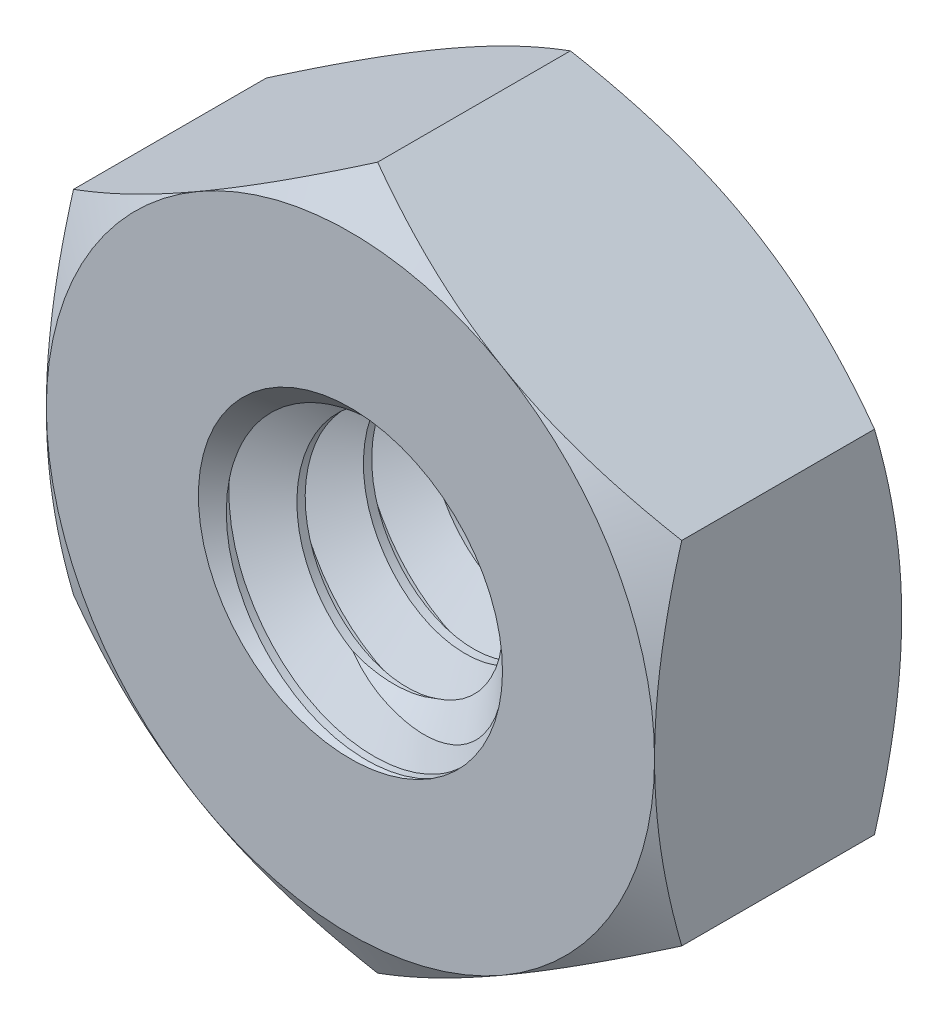
SolidWorks part; units mm, degrees
ref_plane "Front" through (0, 0, 0) normal (0, 0, 1) x (1, 0, 0)
ref_plane "Top" through (0, 0, 0) normal (0, 1, 0) x (1, 0, 0)
ref_plane "Right" through (0, 0, 0) normal (1, 0, 0) x (0, 0, -1)
sketch "Sketch1" plane through (0, 0, 0) normal (0, 0, 1) x (1, 0, 0)
  line L1 (-1.6, 0.9238) -> (-1.6, -0.9238)
  line L2 (-1.6, -0.9238) -> (0, -1.8475)
  line L3 (0, -1.8475) -> (1.6, -0.9238)
  line L4 (1.6, -0.9238) -> (1.6, 0.9238)
  line L5 (1.6, 0.9238) -> (0, 1.8475)
  line L6 (0, 1.8475) -> (-1.6, 0.9238)
  circle A0 centre (0, 0) radius 1.6 construction
  circle A1 centre (0, 0) radius 0.8 construction
  point P10 (0, 0.8)
  dimension "hex" = 3.2
  dimension "dia" = 1.6
extrude "Extrude1" add sketch "Sketch1" along normal mid plane 1.3
sketch "Sketch4" plane through (0, 0, -0.65) normal (0, 0, -1) x (-1, 0, 0)
  circle A0 centre (0, 0) radius 0.8 construction
  circle A1 centre (0, 0) radius 0.8
sketch "Sketch10" plane through (0, 0, 0.65) normal (0, 0, 1) x (1, 0, 0)
  circle A0 centre (0, 0) radius 0.8 construction
  circle A1 centre (0, 0) radius 0.8
extrude "Cut-Extrude2" cut sketch "Sketch10" against normal through all draft 45
sketch "Sketch11" plane through (0, 0, -0.65) normal (0, 0, -1) x (-1, 0, 0)
  circle A0 centre (0, 0) radius 0.8 construction
  circle A1 centre (0, 0) radius 0.8
extrude "Cut-Extrude3" cut sketch "Sketch11" against normal through all draft 45
sketch "Sketch13" plane through (0, 0, -0.65) normal (0, 0, -1) x (-1, 0, 0)
  circle A0 centre (0, 0) radius 0.8 construction
  circle A1 centre (0, 0) radius 0.8
extrude "Boss-Extrude1" add sketch "Sketch13" against normal up to vertex (1.3 mm away) separate body up to point (-1.6, 0.9238, 0.65)
curve "Helix/Spiral3" pitch 0.35 height 1.3 radius 0.8 centre (0, 0, -0.65) axis (0, 0, 1) start towards (0, 1, 0)
sketch "Sketch12" plane through (0, 0, 0) normal (1, 0, 0) x (0, 0, -1)
  line L0 (0.9563, 0.8) -> (0.65, 0.8)
  line L1 (0.9563, 0.8) -> (0.825, 0.5727)
  line L2 (0.825, 0.5727) -> (0.7813, 0.5727)
  line L3 (0.7813, 0.5727) -> (0.65, 0.8)
  line L4 (0.8031, 0.5727) -> (0.8031, 0.8) construction
  line L5 (0.7156, 0.6863) -> (0.8906, 0.6863) construction
  dimension "D1" = 60
  dimension "D2" = 0.0437
  dimension "D3" = 0.175
sweep "Cut-Sweep1" cut profiles "Sketch12" path "Helix/Spiral3" align with end faces yes
combine bodies "Combine1" operation type subtract main body 116 bodies to subtract 118
sketch "Sketch7" plane through (0, 0, 0.65) normal (0, 0, 1) x (1, 0, 0)
  circle A0 centre (0, 0) radius 1.6 construction
  circle A1 centre (0, 0) radius 1.6
extrude "Extrude2" cut sketch "Sketch7" against normal blind 25.4 draft 60 flip side to cut
mirror "Mirror2" about plane through (0, 0, 0) normal (0, 0, 1) of "Extrude2"
sketch "Sketch8" plane through (0, 0, 0.65) normal (0, 0, 1) x (1, 0, 0)
  line L0 (-0.5657, 0.5657) -> (0, 0) construction
  line L1 (0, -0.8678) -> (0, 0.8678) construction
  circle A1 centre (0, 0) radius 0.8 construction
  point P0 (-0.5657, 0.5657)
  dimension "D1" = 45
equation "\"D3@Helix/Spiral3\" = \"length@Extrude1\" "
equation "\"D2@Sketch12\" = \"D4@Helix/Spiral3\"*.125"
equation "\"D3@Sketch12\" = \"D4@Helix/Spiral3\"*.50"
